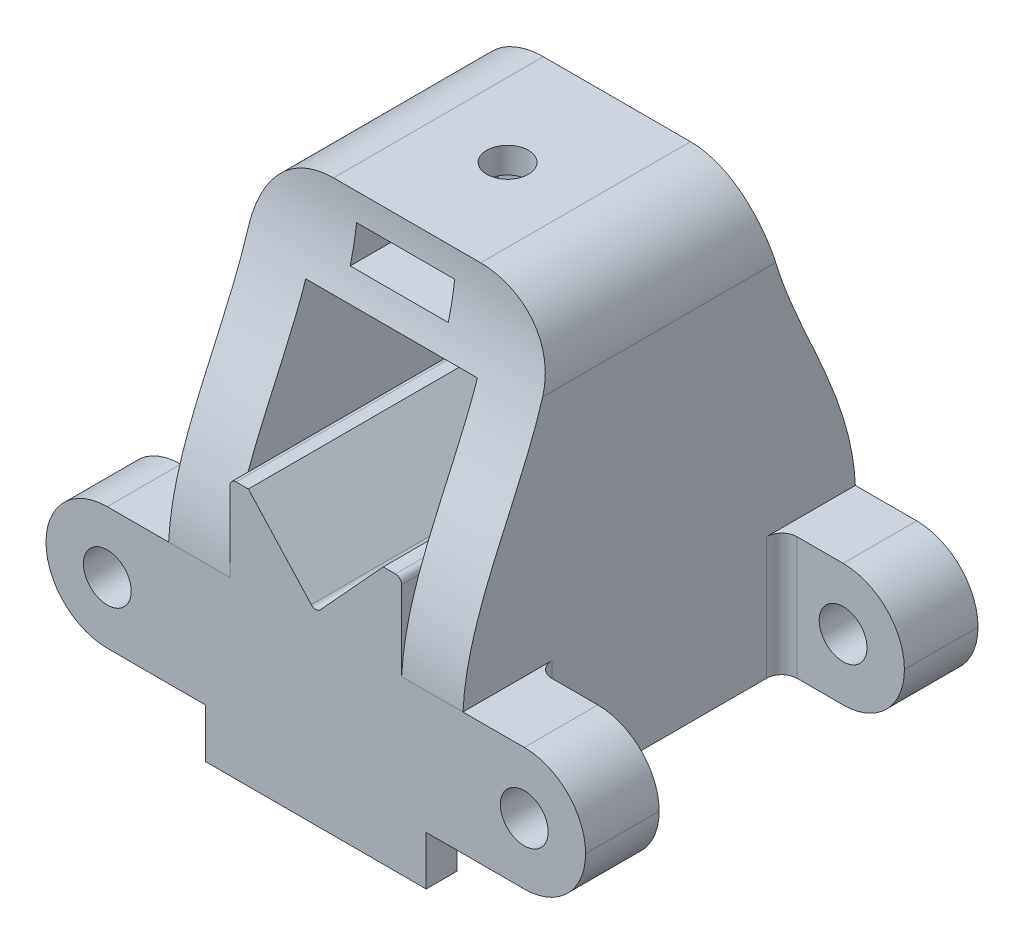
SolidWorks part; units mm, degrees
ref_plane "Front Plane" through (0, 0, 0) normal (0, 0, 1) x (1, 0, 0)
ref_plane "Top Plane" through (0, 0, 0) normal (0, 1, 0) x (1, 0, 0)
ref_plane "Right Plane" through (0, 0, 0) normal (1, 0, 0) x (0, 0, -1)
sketch "Sketch1" plane through (0, 0, 0) normal (0, 1, 0) x (1, 0, 0)
  line L1 (-17.7699, -26) -> (-17.7699, -20)
  line L2 (-17.7699, 6) -> (26.2301, 6)
  line L3 (26.2301, 6) -> (26.2301, 0)
  line L4 (26.2301, 0) -> (16.2301, 0)
  line L5 (16.2301, 0) -> (16.2301, -20)
  line L6 (16.2301, -20) -> (26.2301, -20)
  line L7 (26.2301, -20) -> (26.2301, -26)
  line L8 (26.2301, -26) -> (-17.7699, -26)
  line L10 (-17.7699, -20) -> (-7.7699, -20)
  line L11 (-7.7699, -20) -> (-7.7699, 0)
  line L12 (-7.7699, 0) -> (-17.7699, 0)
  line L13 (-17.7699, 0) -> (-17.7699, 6)
  dimension "D1" = 6
  dimension "D2" = 20
  dimension "D3" = 10
  dimension "D4" = 6
  dimension "D5" = 10
  dimension "D6" = 10
  dimension "D7" = 10
  dimension "D8" = 24
extrude "Boss-Extrude1" add sketch "Sketch1" along normal blind 10
sketch "Sketch2" plane through (0, 10, 0) normal (0, 1, 0) x (1, 0, 0)
  line L0 (26.2301, 6) -> (-17.7699, 6) construction
  line L1 (-7.7699, 6) -> (-2.7699, 6)
  line L2 (-7.7699, 6) -> (-7.7699, -26)
  line L3 (-7.7699, -26) -> (-2.7699, -26)
  line L4 (-2.7699, 6) -> (-2.7699, -26)
  line L5 (-17.7699, -26) -> (26.2301, -26) construction
  line L6 (-7.7699, 0) -> (-7.7699, -20) construction
  line L7 (16.2301, 6) -> (11.2301, 6)
  line L8 (16.2301, 6) -> (16.2301, -26)
  line L9 (16.2301, -26) -> (11.2301, -26)
  line L10 (11.2301, 6) -> (11.2301, -26)
  line L11 (16.2301, -20) -> (16.2301, 0) construction
  dimension "D1" = 5
  dimension "D2" = 5
extrude "Boss-Extrude2" add sketch "Sketch2" along normal blind 18
sketch "Sketch3" plane through (0, 28, 0) normal (0, 1, 0) x (1, 0, 0)
  line L1 (16.2301, -20) -> (-7.7699, -20)
  line L2 (16.2301, -20) -> (16.2301, 0)
  line L3 (16.2301, 0) -> (-7.7699, 0)
  line L4 (-7.7699, -20) -> (-7.7699, 0)
extrude "Boss-Extrude3" add sketch "Sketch3" along normal blind 7
sketch "Sketch4" plane through (16.2301, 0, 0) normal (1, 0, 0) x (0, 0, -1)
  line L0 (-20, 35) -> (0, 35) construction
  line L1 (-10, 35) -> (-10, 0) construction
  line L2 (-20, 0) -> (0, 0) construction
  line L3 (-26, 10) -> (-26, 35)
  line L4 (-26, 35) -> (-18.5551, 35)
  line L5 (6, 10) -> (6, 35)
  line L6 (6, 35) -> (-1.4449, 35)
  spline S0 degree 3 poles (-26, 10) (-25.5554, 18.8789) (-18.5296, 25.9558) (-18.5551, 35) knots 0 0 0 0 1 1 1 1
  spline S1 degree 3 poles (6, 10) (5.5554, 18.8789) (-1.4704, 25.9558) (-1.4449, 35) knots 0 0 0 0 1 1 1 1
extrude "Cut-Extrude1" cut sketch "Sketch4" against normal through all
sketch "Sketch5" plane through (0, 0, 26) normal (0, 0, 1) x (1, 0, 0)
  line L1 (-2.7699, 10) -> (11.2301, 10)
  line L2 (-2.7699, 10) -> (-2.7699, 16.5)
  line L3 (-2.2699, 17) -> (-1.2699, 17)
  line L4 (11.2301, 10) -> (11.2301, 16.5)
  line L6 (4.2301, 10) -> (4.2301, 24.8594) construction
  line L7 (-1.2699, 17) -> (3.8615, 11.4021)
  line L8 (4.5986, 11.4021) -> (9.7301, 17)
  line L9 (9.7301, 17) -> (10.7301, 17)
  arc A1 (3.8615, 11.4021) -> (4.5986, 11.4021) centre (4.2301, 11.7399) ccw
  arc A2 (10.7301, 17) -> (11.2301, 16.5) centre (10.7301, 16.5) cw
  arc A3 (-2.7699, 16.5) -> (-2.2699, 17) centre (-2.2699, 16.5) cw
  point P15 (4.2301, 11)
  point P18 (11.2301, 17)
  point P21 (-2.7699, 17)
  dimension "D4" = 1.5
  dimension "D7" = 0.5
  dimension "D8" = 0.5
  dimension "D1" = 14
  dimension "D2" = 7
  dimension "D5" = 1.5
  dimension "D6" = 1
extrude "Boss-Extrude4" add sketch "Sketch5" against normal up to surface (32 mm away) up to face at (4.2301, 7.5, -6)
ref_plane "Plane1" through (0, 0, 20.5) normal (0, 0, 1) x (1, 0, 0)
sketch "Sketch6" plane through (0, 0, 20.5) normal (0, 0, 1) x (1, 0, 0)
  line L0 (-7.7699, 35) -> (-7.7699, 10) construction
  line L1 (0.2301, 30.1) -> (8.2301, 30.1)
  line L2 (0.2301, 30.1) -> (0.2301, 32.9)
  line L3 (0.2301, 32.9) -> (8.2301, 32.9)
  line L4 (8.2301, 30.1) -> (8.2301, 32.9)
  line L5 (11.2301, 28) -> (-2.7699, 28) construction
  dimension "D1" = 2.8
  dimension "D2" = 8
  dimension "D3" = 8
  dimension "D4" = 2.1
sketch "Sketch7" plane through (0, 35, 0) normal (0, 1, 0) x (1, 0, 0)
  line L0 (-7.7699, -1.4449) -> (-7.7699, -18.5551) construction
  line L1 (16.2301, -18.5551) -> (-7.7699, -18.5551) construction
  circle A0 centre (4.2301, -10.3601) radius 1.7
  dimension "D1" = 12
  dimension "D2" = 8.195
extrude "Cut-Extrude2" cut sketch "Sketch7" against normal up to surface (7 mm away) up to face at (4.2301, 28, 10)
extrude "Cut-Extrude3" cut sketch "Sketch6" against normal blind 13.34
sketch "Sketch8" plane through (0, 0, 26) normal (0, 0, 1) x (1, 0, 0)
  line L0 (-17.7699, 0) -> (26.2301, 0) construction
  line L1 (26.2301, 10) -> (26.2301, 0) construction
  line L3 (-17.7699, 10) -> (-17.7699, 0) construction
  circle A0 centre (21.2301, 5) radius 1.95
  circle A1 centre (-12.7699, 5) radius 1.95
  dimension "D1" = 5
  dimension "D2" = 5
  dimension "D3" = 5
  dimension "D4" = 5
extrude "Cut-Extrude4" cut sketch "Sketch8" against normal through all
fillet "Fillet1" radius 5 8 edges at (-17.7699, 0, -3) (-17.7699, 10, -3) (-17.7699, 0, 23) (-17.7699, 10, 23) (26.2301, 10, -3) (26.2301, 0, -3) (26.2301, 0, 23) (26.2301, 10, 23)
fillet "Fillet2" radius 1.25 4 edges at (16.2301, 5, 20) (16.2301, 5, 0) (-7.7699, 5, 20) (-7.7699, 5, 0)
fillet "Fillet3" radius 6 2 edges at (16.2301, 35, 10) (-7.7699, 35, 10)
sketch "Sketch9" plane through (0, 0, 0) normal (0, -1, 0) x (1, 0, 0)
  line L0 (-12.7699, 26) -> (21.2301, 26) construction
  line L1 (-4.7699, 26) -> (13.2301, 26)
  line L2 (-4.7699, 26) -> (-4.7699, 23.5)
  line L3 (-4.7699, 23.5) -> (13.2301, 23.5)
  line L4 (13.2301, 26) -> (13.2301, 23.5)
  line L5 (-7.7699, 1.25) -> (-7.7699, 18.75) construction
  dimension "D1" = 18
  dimension "D2" = 2.5
  dimension "D3" = 3
extrude "Boss-Extrude5" add sketch "Sketch9" along normal blind 4 contours L2 L3 L4 L1
fillet "Fillet4" radius 1 1 edges at (4.2301, 0, 23.5)
